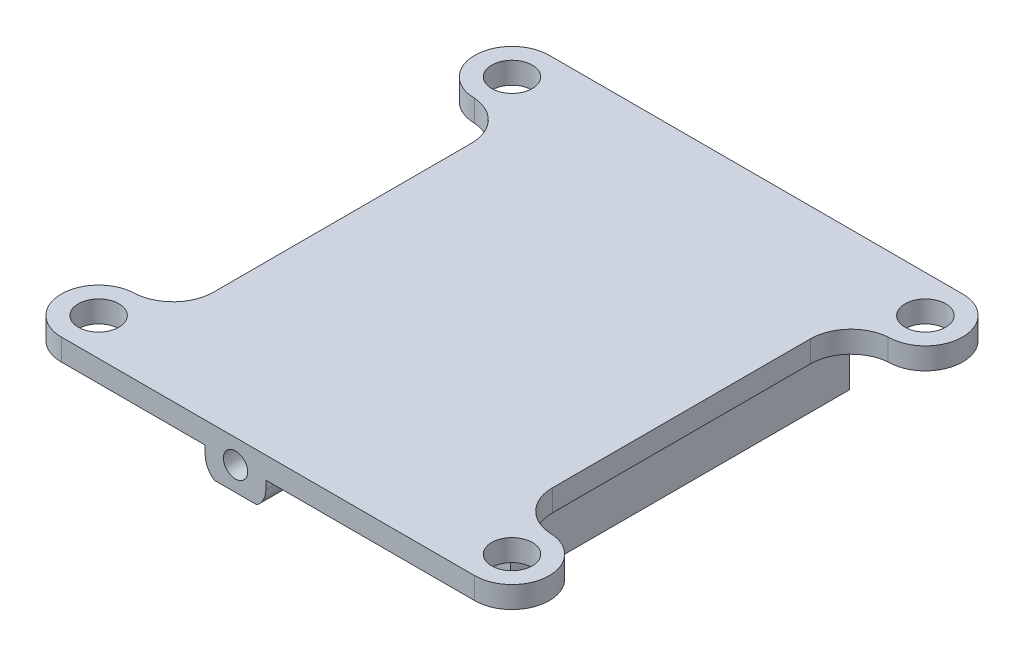
SolidWorks part; units mm, degrees
ref_plane "Front Plane" through (0, 0, 0) normal (0, 0, 1) x (1, 0, 0)
ref_plane "Top Plane" through (0, 0, 0) normal (0, 1, 0) x (1, 0, 0)
ref_plane "Right Plane" through (0, 0, 0) normal (1, 0, 0) x (0, 0, -1)
sketch "Sketch1" plane through (0, 0, 0) normal (0, 1, 0) x (1, 0, 0)
  line L0 (0, 14.2402) -> (0, -22.8173) construction
  line L1 (-20.2546, 0) -> (19.294, 0) construction
  line L2 (-12.5, -9.5104) -> (-12.5, 9.5104)
  line L11 (-15.25, -18) -> (15.25, -18)
  line L13 (-15.25, 18) -> (15.25, 18)
  line L15 (-15.25, -15.25) -> (15.25, 15.25) construction
  line L16 (-15.25, 15.25) -> (15.25, -15.25) construction
  line L17 (12.5, -9.5104) -> (12.5, 9.5104)
  line L19 (-12.4, 12.5) -> (12.4, 12.5)
  line L20 (-12.4, 12.5) -> (-12.4, -12.5)
  line L21 (-12.4, -12.5) -> (12.4, -12.5)
  line L22 (12.4, 12.5) -> (12.4, -12.5)
  line L23 (-12.4, 12.5) -> (12.4, -12.5) construction
  line L24 (-12.4, -12.5) -> (12.4, 12.5) construction
  circle A0 centre (-15.25, 15.25) radius 1.5
  circle A1 centre (15.25, 15.25) radius 1.5
  circle A2 centre (15.25, -15.25) radius 1.5
  circle A3 centre (-15.25, -15.25) radius 1.5
  circle A4 centre (-15.25, 15.25) radius 2.75
  circle A5 centre (15.25, 15.25) radius 2.75
  circle A6 centre (-15.25, -15.25) radius 2.75
  circle A7 centre (15.25, -15.25) radius 2.75
  arc A8 (-12.5, 9.5104) -> (-15.25, 12.5) centre (-15.5, 9.5104) ccw
  arc A9 (12.5, 9.5104) -> (15.25, 12.5) centre (15.5, 9.5104) cw
  arc A10 (12.5, -9.5104) -> (15.25, -12.5) centre (15.5, -9.5104) ccw
  arc A11 (-12.5, -9.5104) -> (-15.25, -12.5) centre (-15.5, -9.5104) cw
  point P7 (0, 0)
  point P8 (0, 0)
  point P36 (12.5, 0)
  point P37 (-12.5, 0)
  point P39 (0, 0)
  dimension "D1" = 3
  dimension "D3" = 5.5
  dimension "D6" = 3
  dimension "D2" = 30.5
  dimension "D4" = 36
  dimension "D5" = 30.5
  dimension "D7" = 0.1
extrude "Boss-Extrude1" add sketch "Sketch1" along normal blind 1.6 contours L2 A11 A6 L11 A7 A10 L17 A9 A5 L13 A4 A8 | A5 A1 | A4 A0 | A6 A3 | A7 A2 | L20 L19 L22 L21 region at (-12.4528, 0, 0) region at (-13.3605, 0, 13.3605) region at (-17.9222, 0, -15.25) region at (12.5778, 0, 15.25) region at (17.1395, 0, -17.1395)
extrude "Boss-Extrude2" add sketch "Sketch1<3>" against normal blind 3.2 contours L22 L19 L20 L21 region at (0, 0, 0)
sketch "Sketch1<3>" plane through (0, 0, 0) normal (0, 1, 0) x (1, 0, 0) same geometry as "Sketch1"
sketch "Sketch2" plane through (0, 0, 18) normal (0, 0, 1) x (1, 0, 0)
  line L0 (-2.4, 8.1739) -> (-2.4, -13.1813) construction
  line L1 (-12.4, -3.2) -> (-12.4, 0) construction
  line L2 (-12.4, 0) -> (12.4, 0) construction
  line L3 (-12.4, 0) -> (12.4, 0) construction
  line L4 (-4.635, 0) -> (-4.1, 0)
  line L5 (-4.635, 0) -> (-4.635, -0.6302)
  line L6 (-3.9652, -1.91) -> (-0.8348, -1.91)
  line L7 (-0.165, 0) -> (-0.165, -0.6302)
  line L8 (-0.165, 0) -> (-0.7, 0)
  line L9 (-4.1, 0) -> (-4.1, 1.6)
  line L10 (-4.1, 1.6) -> (-0.7, 1.6)
  line L11 (-15.25, 1.6) -> (15.25, 1.6) construction
  line L12 (-0.7, 0) -> (-0.7, 1.6)
  arc A0 (-4.635, -0.6302) -> (-3.9652, -1.91) centre (-3.0773, -0.6302) ccw
  circle A1 centre (-2.4, -0.15) radius 0.8958
  arc A2 (-0.165, -0.6302) -> (-0.8348, -1.91) centre (-1.7227, -0.6302) cw
  point P4 (-12.4, -1.6)
  point P7 (-2.4, 0)
  point P20 (-4.1, 0.8)
  point P26 (-2.4, -1.91)
  point P31 (-2.4, 1.6)
  line M16 (-15.25, 0) -> (15.25, 0)
  dimension "D1" = 10
  dimension "D2" = 3.51
  dimension "D3" = 3.4
  dimension "D4" = 4.47
  dimension "D5" = 1.75
  dimension "D6" = 0.15
extrude "Boss-Extrude3" add sketch "Sketch2" against normal up to surface (5.5 mm away) up to face at (0, -1.6, 12.5)
extrude "Cut-Extrude1" cut sketch "Sketch2<2>" against normal up to surface (5.5 mm away) contours A1 M16 | A1 M16 region at (-2.4, -0.4505, 18) region at (-2.4, 0.3125, 18) up to face at (-1.44, -1.1645, 12.5)
sketch "Sketch2<2>" plane through (0, 0, 18) normal (0, 0, 1) x (1, 0, 0) same geometry as "Sketch2"
